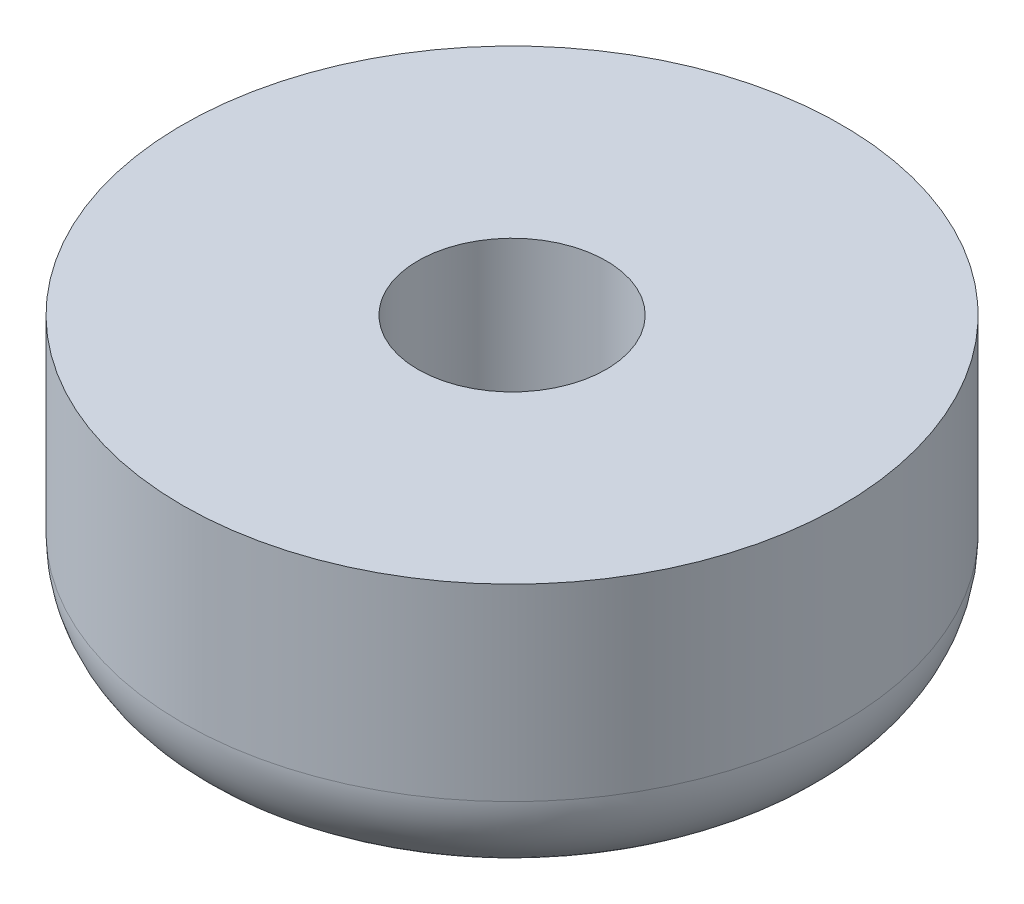
SolidWorks part; units mm, degrees
ref_plane "Front Plane" through (0, 0, 0) normal (0, 0, 1) x (1, 0, 0)
ref_plane "Top Plane" through (0, 0, 0) normal (0, 1, 0) x (1, 0, 0)
ref_plane "Right Plane" through (0, 0, 0) normal (1, 0, 0) x (0, 0, -1)
sketch "Sketch1" plane through (0, 0, 0) normal (0, 1, 0) x (1, 0, 0)
  circle A0 centre (0, 0) radius 3.5
  dimension "D1" = 7
extrude "Boss-Extrude1" add sketch "Sketch1" along normal blind 3
sketch "Sketch2" plane through (0, 3, 0) normal (0, 1, 0) x (1, 0, 0)
  circle A0 centre (0, 0) radius 1
  dimension "D1" = 2
extrude "Cut-Extrude1" cut sketch "Sketch2" against normal blind 2
fillet "Fillet1" radius 1 1 edges at (0, 0, 3.5)
